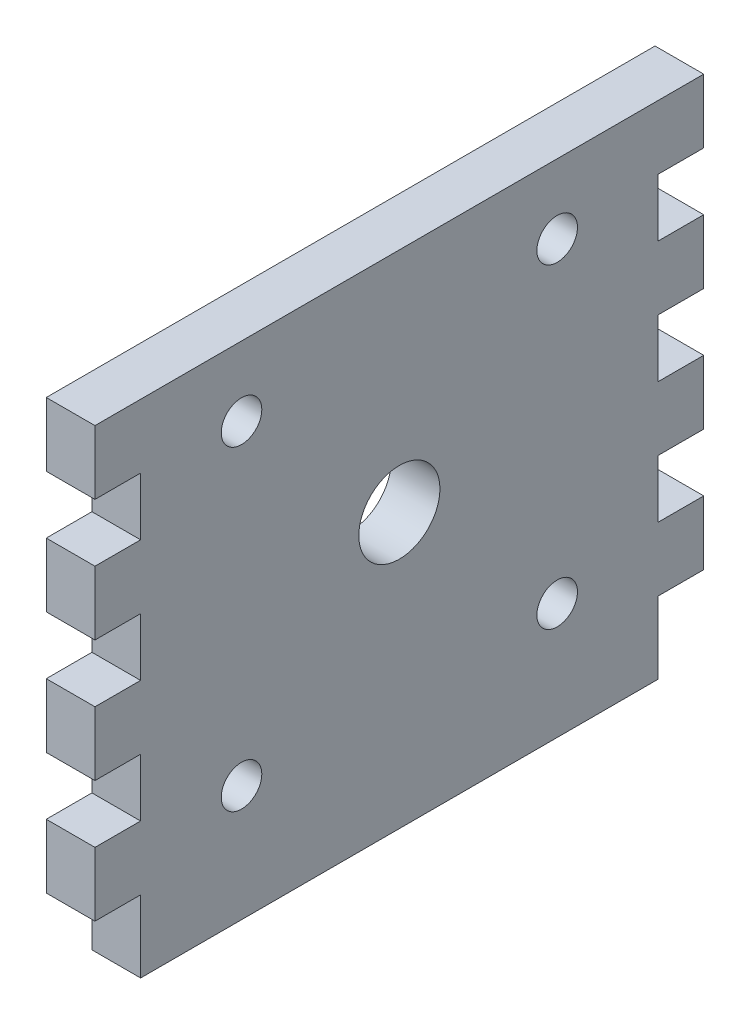
SolidWorks part; units mm, degrees
material "Thornel VCB-20 Carbon Cloth"
ref_plane "Front Plane" through (0, 0, 0) normal (0, 0, 1) x (1, 0, 0)
ref_plane "Top Plane" through (0, 0, 0) normal (0, 1, 0) x (1, 0, 0)
ref_plane "Right Plane" through (0, 0, 0) normal (1, 0, 0) x (0, 0, -1)
sketch "Sketch1" plane through (0, 0, 0) normal (1, 0, 0) x (0, 0, -1)
  line L1 (-36.7425, 26.5162) -> (39.4575, 26.5162)
  line L2 (-36.7425, 26.5162) -> (-36.7425, -36.2218)
  line L3 (-36.7425, -36.2218) -> (39.4575, -36.2218)
  line L4 (39.4575, 26.5162) -> (39.4575, -36.2218)
  dimension "D1" = 76.2
  dimension "D2" = 62.738
extrude "Boss-Extrude1" add sketch "Sketch1" along normal blind 6.096
sketch "Sketch2" plane through (6.096, 0, 0) normal (1, 0, 0) x (0, 0, -1)
  line L0 (-18.3991, 17.8247) -> (1.3575, -1.9318) construction
  line L2 (1.3575, -1.9318) -> (1.3575, 17.7349) construction
  line L3 (1.3575, 17.7349) -> (1.3575, -22.7612) construction
  line L4 (1.3575, -1.9318) -> (25.6979, -1.9318) construction
  line L5 (25.6979, -1.9318) -> (-22.0212, -1.9318) construction
  line L6 (1.3575, -1.9318) -> (21.114, 17.8247) construction
  line L7 (1.3575, -1.9318) -> (21.114, -21.6884) construction
  line L8 (1.3575, -1.9318) -> (-18.3991, -21.6884) construction
  line L9 (-36.7425, 26.5162) -> (-36.7425, -36.2218) construction
  line L10 (-36.7425, -36.2218) -> (39.4575, -36.2218) construction
  circle A0 centre (1.3575, -1.9318) radius 5.08
  circle A1 centre (-18.3991, 17.8247) radius 2.54
  circle A2 centre (21.114, 17.8247) radius 2.54
  circle A3 centre (21.114, -21.6884) radius 2.54
  circle A4 centre (-18.3991, -21.6884) radius 2.54
  dimension "D1" = 27.94
  dimension "D2" = 45
  dimension "D3" = 27.94
  dimension "D4" = 45
  dimension "D5" = 45
  dimension "D6" = 45
  dimension "D7" = 27.94
  dimension "D8" = 27.94
  dimension "D9" = 38.1
  dimension "D10" = 34.29
extrude "Cut-Extrude1" cut sketch "Sketch2" against normal up to surface (6.096 mm away) up to face at (0, -4.8528, -1.3575)
sketch "Sketch3" plane through (6.096, 0, 0) normal (1, 0, 0) x (0, 0, -1)
  line L0 (-36.7425, 18.5152) -> (-31.0275, 18.5152)
  line L1 (-36.7425, 26.5162) -> (-36.7425, -36.2218) construction
  line L2 (-31.0275, 18.5152) -> (-31.0275, 11.2762)
  line L4 (-31.0275, 11.2762) -> (-36.7425, 11.2762)
  line L9 (39.4575, 26.5162) -> (-36.7425, 26.5162) construction
  line L10 (-36.7425, 3.2752) -> (-31.0275, 3.2752)
  line L11 (-31.0275, 3.2752) -> (-31.0275, -3.9638)
  line L12 (-31.0275, -3.9638) -> (-36.7425, -3.9638)
  line L17 (-36.7425, -11.9648) -> (-31.0275, -11.9648)
  line L18 (-31.0275, -11.9648) -> (-31.0275, -19.2038)
  line L19 (-31.0275, -19.2038) -> (-36.7425, -19.2038)
  line L23 (1.3575, -1.9318) -> (1.3575, -36.2218) construction
  line L24 (-36.7425, -36.2218) -> (39.4575, -36.2218) construction
  line L25 (1.3575, -36.2218) -> (1.3575, 26.5162) construction
  line L26 (-36.7425, 18.5152) -> (-36.7425, 11.2762)
  line L27 (-36.7425, 3.2752) -> (-36.7425, -3.9638)
  line L29 (33.7425, -19.2038) -> (39.4575, -19.2038)
  line L30 (33.7425, -11.9648) -> (33.7425, -19.2038)
  line L31 (39.4575, -11.9648) -> (33.7425, -11.9648)
  line L32 (-36.7425, -11.9648) -> (-36.7425, -19.2038)
  line L34 (39.4575, 18.5152) -> (39.4575, 11.2762)
  line L36 (33.7425, -3.9638) -> (39.4575, -3.9638)
  line L37 (33.7425, 3.2752) -> (33.7425, -3.9638)
  line L38 (39.4575, 3.2752) -> (33.7425, 3.2752)
  line L41 (39.4575, 3.2752) -> (39.4575, -3.9638)
  line L43 (33.7425, 11.2762) -> (39.4575, 11.2762)
  line L44 (39.4575, -11.9648) -> (39.4575, -19.2038)
  line L45 (33.7425, 18.5152) -> (33.7425, 11.2762)
  line L46 (39.4575, 18.5152) -> (33.7425, 18.5152)
  dimension "D1" = 8.001
  dimension "D2" = 5.715
  dimension "D3" = 7.239
  dimension "D4" = 8.001
  dimension "D5" = 3
extrude "Cut-Extrude2" cut sketch "Sketch3" against normal up to surface (6.096 mm away) up to face at (0, -21.6884, 15.8591)
sketch "Sketch4" plane through (6.096, 0, 0) normal (1, 0, 0) x (0, 0, -1)
  line L5 (-36.7425, -36.2218) -> (-31.0275, -36.2218)
  line L6 (-36.7425, -36.2218) -> (-36.7425, -27.2048)
  line L7 (-36.7425, -27.2048) -> (-31.0275, -27.2048)
  line L8 (-31.0275, -36.2218) -> (-31.0275, -27.2048)
  line L9 (1.3575, -1.9318) -> (1.3575, 30.0478)
  line L10 (1.3575, 30.0478) -> (1.3575, -34.4123)
  line L11 (33.7425, -36.2218) -> (33.7425, -27.2048)
  line L12 (39.4575, -27.2048) -> (33.7425, -27.2048)
  line L13 (39.4575, -36.2218) -> (39.4575, -27.2048)
  line L14 (39.4575, -36.2218) -> (33.7425, -36.2218)
  line M21 (-36.7425, -36.2218) -> (39.4575, -36.2218)
  line M22 (39.4575, -36.2218) -> (39.4575, -19.2038)
  dimension "D1" = 5.715
  dimension "D2" = 9.017
extrude "Cut-Extrude3" cut sketch "Sketch4" against normal up to surface (6.096 mm away) and the other way blind 7.874 contours L12 L11 M22 M21 | L7 L8 L5 L6 region at (6.096, -31.7133, -36.6) up to face at (0, -0.9884, -1.3575)
